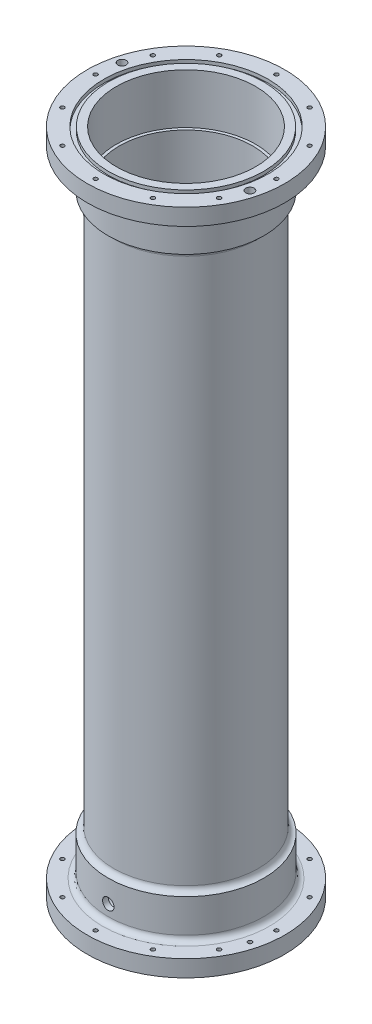
SolidWorks part; units mm, degrees
material "7075-T6 (SN)"
ref_plane "Front Plane" through (0, 0, 0) normal (0, 0, 1) x (1, 0, 0)
ref_plane "Top Plane" through (0, 0, 0) normal (0, 1, 0) x (1, 0, 0)
ref_plane "Right Plane" through (0, 0, 0) normal (1, 0, 0) x (0, 0, -1)
sketch "Sketch2" plane through (0, 0, 0) normal (0, 1, 0) x (1, 0, 0)
  circle A0 centre (0, 0) radius 38.1
  circle A1 centre (0, 0) radius 41.275
  dimension "D1" = 82.55
  dimension "D2" = 76.2
extrude "Base Cylinder" add sketch "Sketch2" along normal blind 381
sketch "Sketch3" plane through (0, 0, 0) normal (0, -1, 0) x (1, 0, 0)
  circle A0 centre (0, 0) radius 38.1
  circle A1 centre (0, 0) radius 56.3562
  dimension "D1" = 112.7125
extrude "Aft Flange" add sketch "Sketch3" against normal blind 9.525
sketch "Sketch34" plane through (0, 0, 0) normal (0, -1, 0) x (1, 0, 0)
  circle A0 centre (0, 0) radius 39.75
  dimension "D1" = 79.5
extrude "TemperatureInsert" cut sketch "Sketch34" against normal blind 28.575
sketch "Sketch6" plane through (0, 0, 0) normal (0, -1, 0) x (1, 0, 0)
  circle A0 centre (0, 0) radius 46.9011
  circle A1 centre (0, 0) radius 44.2849
  dimension "D1" = 93.8022
  dimension "D2" = 88.5698
extrude "Aft O-Ring" cut sketch "Sketch6" against normal blind 1.9812
sketch "Sketch33" plane through (0, 9.525, 0) normal (0, 1, 0) x (1, 0, 0)
  circle A0 centre (0, 0) radius 41.275
  circle A1 centre (0, 0) radius 44.45
  dimension "D1" = 82.55
  dimension "D2" = 88.9
extrude "CriticalBoss" add sketch "Sketch33" along normal blind 22.225
fillet "Fillet1" radius 3.175 2 edges at (0, 9.525, -44.45) (0, 31.75, 41.275)
sketch "Sketch For Bolt Holes" plane through (0, 0, 0) normal (0, -1, 0) x (1, 0, 0)
  circle A0 centre (-51.6255, 0) radius 1.5875
  circle A1 centre (-44.709, 25.8128) radius 1.5875
  circle A2 centre (-25.8128, 44.709) radius 1.5875
  circle A3 centre (0, 51.6255) radius 1.5875
  circle A4 centre (25.8127, 44.709) radius 1.5875
  circle A5 centre (44.709, 25.8128) radius 1.5875
  circle A6 centre (51.6255, 0) radius 1.5875
  circle A7 centre (44.709, -25.8127) radius 1.5875
  circle A8 centre (25.8128, -44.709) radius 1.5875
  circle A9 centre (0, -51.6255) radius 1.5875
  circle A10 centre (-25.8127, -44.709) radius 1.5875
  circle A11 centre (-44.709, -25.8128) radius 1.5875
  point P36 (0, 0)
  dimension "D2" = 3.175
  dimension "D1" = 51.6255
  dimension "D3" = 12
hole_wizard "Bolt Circle" positions "Sketch8" profile "Sketch9" hole size "#4-40" standard "ANSI Inch" end condition up to next
sketch "Sketch8" plane through (0, 0, 0) normal (0, -1, 0) x (-1, 0, 0)
  point P0 (-25.8127, -44.709)
  point P3 (-44.709, -25.8128)
  point P6 (-51.6255, 0)
  point P9 (-44.709, 25.8127)
  point P12 (-25.8128, 44.709)
  point P15 (0, 51.6255)
  point P18 (25.8127, 44.709)
  point P21 (44.709, 25.8128)
  point P24 (51.6255, 0)
  point P27 (44.709, -25.8128)
  point P30 (25.8128, -44.709)
  point P33 (0, -51.6255)
  point P36 (-25.8127, -44.709)
  point P38 (-44.709, -25.8128)
  point P40 (-51.6255, 0)
sketch "Sketch9" plane through (25.8127, 0, 44.709) normal (1, 0, 0) x (0, 0, -1)
  line L0 (0, 0) -> (0, 381)
  line L1 (0, 381) -> (1.1303, 381)
  line L2 (1.1303, 381) -> (1.1303, 0)
  line L5 (1.1303, 0) -> (0, 0)
  line L11 (0, -6.35) -> (0, 107.95) construction
  dimension "Thru Hole Dia." = 2.2606
  dimension "Thru Hole Depth" = 381
sketch "Dowel Hole Sketch" plane through (0, 0, 0) normal (0, -1, 0) x (1, 0, 0)
  line L0 (0, 0) -> (-51.6255, 0) construction
  line L1 (0, 0) -> (-49.8664, -13.3617) construction
  line L2 (0, 0) -> (0, -51.6255) construction
  line L3 (0, 0) -> (49.8664, 13.3617) construction
  circle A0 centre (0, 0) radius 51.6255
  circle A1 centre (-49.8664, -13.3617) radius 4.6172
  circle A2 centre (49.8664, 13.3617) radius 3.4532
  dimension "D1" = 15
hole_wizard "Hole1" positions "Sketch14" profile "Sketch12" legacy end condition up to next
sketch "Sketch14" plane through (0, 0, 0) normal (0, -1, 0) x (-1, 0, 0)
  point P0 (49.8664, 13.3617)
  point P3 (-49.8664, -13.3617)
sketch "Sketch12" plane through (-49.8664, 0, -13.3617) normal (1, 0, 0) x (0, 0, -1)
  line L0 (0, 0) -> (0, 381)
  line L1 (0, 381) -> (1.1906, 381)
  line L2 (1.1906, 381) -> (1.1906, 4.7625)
  line L3 (1.1906, 4.7625) -> (2.3813, 4.7625)
  line L4 (2.3813, 4.7625) -> (2.3813, 0)
  line L5 (2.3813, 0) -> (0, 0)
  line L6 (0, 110) -> (0, -10) construction
  dimension "Diameter" = 2.3813
  dimension "Depth" = 381
  dimension "C-Bore Diameter" = 4.7625
  dimension "C-Bore Depth" = 4.7625
ref_plane "Hoop Mid-Plane" through (0, 190.5, 0) normal (0, 1, 0) x (1, 0, 0)
ref_plane "PressureTapHolePlane" through (0, 0, 44.45) normal (0, 0, 1) x (1, 0, 0)
ref_plane "TemperatureTapPlane" through (0, 0, -44.45) normal (0, 0, 1) x (1, 0, 0)
sketch "ThermoHole" plane through (0, 0, -44.45) normal (0, 0, 1) x (1, 0, 0)
  line L0 (-56.3562, 0) -> (56.3562, 0) construction
  circle A0 centre (0, 19.05) radius 3.175
  dimension "D1" = 19.05
  dimension "D2" = 6.35
hole_wizard "1/8 NPT Tapped ThermocoupleHole" positions "Sketch43" profile "Sketch44" size "1/8" standard "ANSI Inch"
sketch "Sketch43" plane through (0, 0, -44.45) normal (0, 0, 1) x (1, 0, 0)
  line L0 (-56.3562, 0) -> (56.3562, 0) construction
  point P0 (0, 19.05)
  dimension "D1" = 19.05
sketch "Sketch44" plane through (0, 19.05, -44.45) normal (1, 0, 0) x (0, 1, 0)
  line L0 (0, 0) -> (0, 14.2175)
  line L1 (4.2164, 11.684) -> (0, 14.2175)
  line L2 (-4.2164, 11.684) -> (0, 14.2175) construction
  line L3 (4.2164, 11.684) -> (4.2164, 6.858)
  line L4 (4.2164, 6.858) -> (4.9362, 6.858)
  line L5 (4.9362, 6.858) -> (5.1415, 0)
  line L6 (-4.9362, 6.858) -> (-5.1415, 0) construction
  line L7 (5.1415, 0) -> (0, 0)
  line L8 (0, -6.35) -> (0, 107.95) construction
  line L11 (-4.2164, 6.858) -> (-4.9362, 6.858) construction
  dimension "Tap Drill Dia." = 8.4328
  dimension "Tap Drill Depth" = 11.684
  dimension "Thread Dia." = 10.283
  dimension "Thread Angle" = 3.43
  dimension "Thread Depth" = 6.858
  dimension "Drill Angle" = 118
mirror "Mirror1" about plane through (0, 190.5, 0) normal (0, 1, 0) of "Hole1", "Bolt Circle", "Fillet1", "CriticalBoss", "Aft O-Ring", "TemperatureInsert", "Aft Flange"
hole_wizard "5/16-18 Tapped Hole1" positions "Sketch48" profile "Sketch49" tap size "5/16-18" standard "ANSI Inch"
sketch "Sketch48" plane through (0, 0, 44.45) normal (0, 0, 1) x (1, 0, 0)
  line L0 (-56.3562, 0) -> (56.3562, 0) construction
  point P0 (0, 19.05)
  dimension "D1" = 19.05
sketch "Sketch49" plane through (0, 19.05, 44.45) normal (1, 0, 0) x (0, -1, 0)
  line L0 (0, 0) -> (0, 5.2631)
  line L1 (0, 5.2631) -> (3.2639, 3.302)
  line L2 (3.2639, 3.302) -> (3.2639, 0)
  line L5 (3.2639, 0) -> (0, 0)
  line L10 (0, 5.2631) -> (-3.2639, 3.302) construction
  line L11 (0, -6.35) -> (0, 107.95) construction
  dimension "Tap Drill Dia." = 6.5278
  dimension "Tap Drill Depth" = 3.302
  dimension "Drill Angle" = 118
sketch "Sketch50" plane through (0, 0, 44.45) normal (0, 0, 1) x (1, 0, 0)
  circle A0 centre (0, 19.05) radius 1.5875
  dimension "D1" = 3.175
extrude "Cut-Extrude1" cut sketch "Sketch50" against normal up to next
